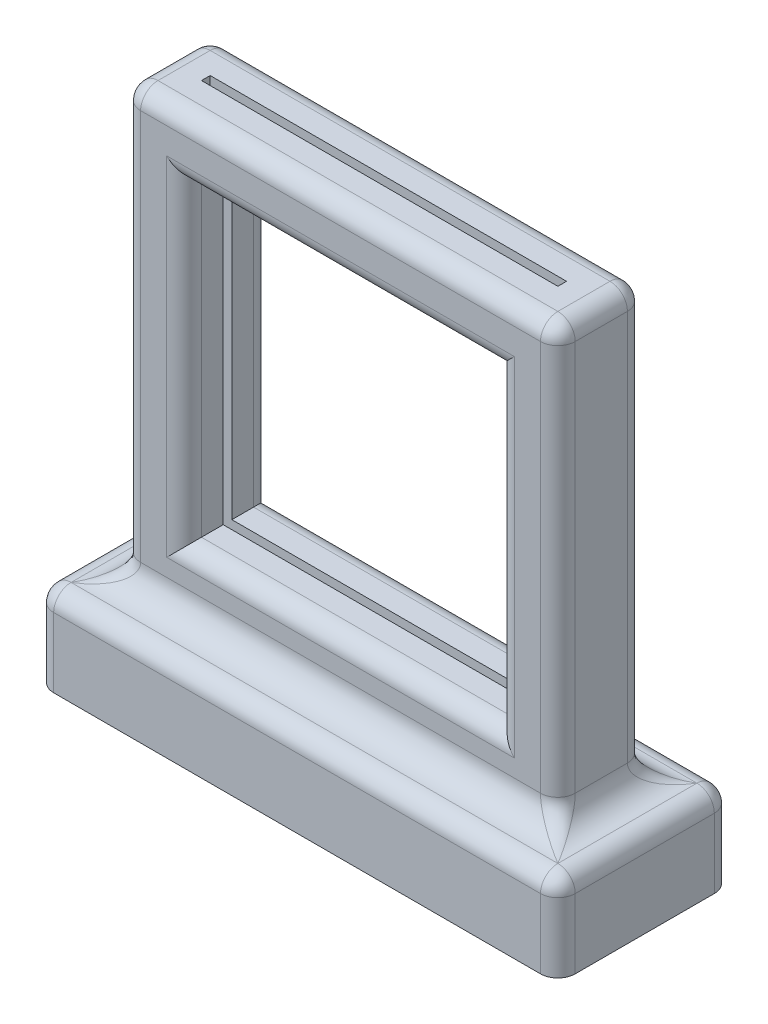
SolidWorks part; units mm, degrees
ref_plane "Front Plane" through (0, 0, 0) normal (0, 0, 1) x (1, 0, 0)
ref_plane "Top Plane" through (0, 0, 0) normal (0, 1, 0) x (1, 0, 0)
ref_plane "Right Plane" through (0, 0, 0) normal (1, 0, 0) x (0, 0, -1)
sketch "Sketch1" plane through (0, 0, 0) normal (0, 1, 0) x (1, 0, 0)
  line L0 (0, 0) -> (76.2, 0)
  line L1 (0, 0) -> (0, 25.4)
  line L2 (0, 25.4) -> (76.2, 25.4)
  line L3 (76.2, 25.4) -> (76.2, 0)
  dimension "D1" = 76.2
  dimension "D2" = 25.4
extrude "Boss-Extrude1" add sketch "Sketch1" along normal blind 12.7 contours L2 L3 L0 L1
sketch "Sketch7" plane through (0, 12.7, 0) normal (0, 1, 0) x (1, 0, 0)
  line L0 (6.35, 19.05) -> (6.35, 6.35)
  line L9 (6.35, 6.35) -> (69.85, 6.35)
  line L10 (69.85, 19.05) -> (69.85, 6.35)
  line L11 (69.85, 19.05) -> (6.35, 19.05)
  line L13 (0, 25.4) -> (76.2, 25.4) construction
  line L14 (0, 0) -> (0, 25.4) construction
  dimension "D1" = 63.5
  dimension "D2" = 12.7
  dimension "D3" = 6.35
  dimension "D4" = 6.35
extrude "Boss-Extrude3" add sketch "Sketch7" along normal blind 63.5 contours L10 L11 L0 L9 region at (38.1, 12.7, -12.7)
sketch "Sketch8" plane through (0, 0, -6.35) normal (0, 0, 1) x (1, 0, 0)
sketch "Sketch10" plane through (0, 0, -6.35) normal (0, 0, 1) x (1, 0, 0)
  line L0 (6.35, 76.2) -> (6.35, 12.7) construction
  line L1 (15.24, 67.31) -> (60.96, 67.31)
  line L2 (15.24, 67.31) -> (15.24, 21.59)
  line L3 (15.24, 21.59) -> (60.96, 21.59)
  line L4 (60.96, 67.31) -> (60.96, 21.59)
  line L5 (6.35, 76.2) -> (69.85, 76.2) construction
  dimension "D1" = 45.72
  dimension "D2" = 45.72
  dimension "D3" = 8.89
  dimension "D4" = 8.89
extrude "Cut-Extrude2" cut sketch "Sketch10" against normal blind 63.5
sketch "Sketch11" plane through (0, 76.2, 0) normal (0, 1, 0) x (1, 0, 0)
  line L1 (12.065, 13.335) -> (64.135, 13.335)
  line L2 (12.065, 13.335) -> (12.065, 12.065)
  line L3 (12.065, 12.065) -> (64.135, 12.065)
  line L4 (64.135, 13.335) -> (64.135, 12.065)
  line L5 (6.35, 19.05) -> (6.35, 6.35) construction
  line L6 (69.85, 19.05) -> (6.35, 19.05) construction
  dimension "D1" = 1.27
  dimension "D2" = 52.07
  dimension "D3" = 5.715
  dimension "D4" = 5.715
extrude "Cut-Extrude3" cut sketch "Sketch11" against normal blind 57.15
fillet "Fillet5" radius 3.81 4 edges at (69.85, 12.7, -12.7) (38.1, 12.7, -19.05) (6.35, 12.7, -12.7) (38.1, 12.7, -6.35)
fillet "Fillet7" radius 2.54 4 edges at (0, 12.7, -12.7) (38.1, 12.7, 0) (76.2, 12.7, -12.7) (38.1, 12.7, -25.4)
fillet "Fillet8" radius 2.54 16 edges at (0, 5.08, -25.4) (0.7439, 11.9561, -24.6561) (5.2341, 13.8159, -20.1659) (0, 5.08, 0) (0.7439, 11.9561, -0.7439) (5.2341, 13.8159, -5.2341) (76.2, 5.08, 0) (75.4561, 11.9561, -0.7439) (70.9659, 13.8159, -5.2341) (76.2, 5.08, -25.4) (75.4561, 11.9561, -24.6561) (70.9659, 13.8159, -20.1659) (6.35, 46.355, -19.05) (6.35, 46.355, -6.35) (69.85, 46.355, -6.35) (69.85, 46.355, -19.05)
fillet "Fillet9" radius 2.54 8 edges at (69.1061, 76.2, -18.3061) (69.85, 76.2, -12.7) (69.1061, 76.2, -7.0939) (38.1, 76.2, -6.35) (7.0939, 76.2, -7.0939) (6.35, 76.2, -12.7) (7.0939, 76.2, -18.3061) (38.1, 76.2, -19.05)
fillet "Fillet11" radius 2.54 8 edges at (60.96, 44.45, -6.35) (38.1, 67.31, -6.35) (15.24, 44.45, -6.35) (38.1, 21.59, -6.35) (60.96, 44.45, -19.05) (15.24, 44.45, -19.05) (38.1, 21.59, -19.05) (38.1, 67.31, -19.05)
sketch "Sketch12" plane through (0, 0, 0) normal (0, -1, 0) x (1, 0, 0)
  line L0 (2.54, 0) -> (73.66, 0) construction
  line L1 (0, -2.54) -> (0, -22.86) construction
  circle A0 centre (38.1, -12.7) radius 9.525
  point P2 (0, 0)
  point P5 (0, 0)
  dimension "D1" = 19.05
  dimension "D2" = 12.7
  dimension "D3" = 38.1
extrude "Cut-Extrude4" cut sketch "Sketch12" against normal blind 3.302
